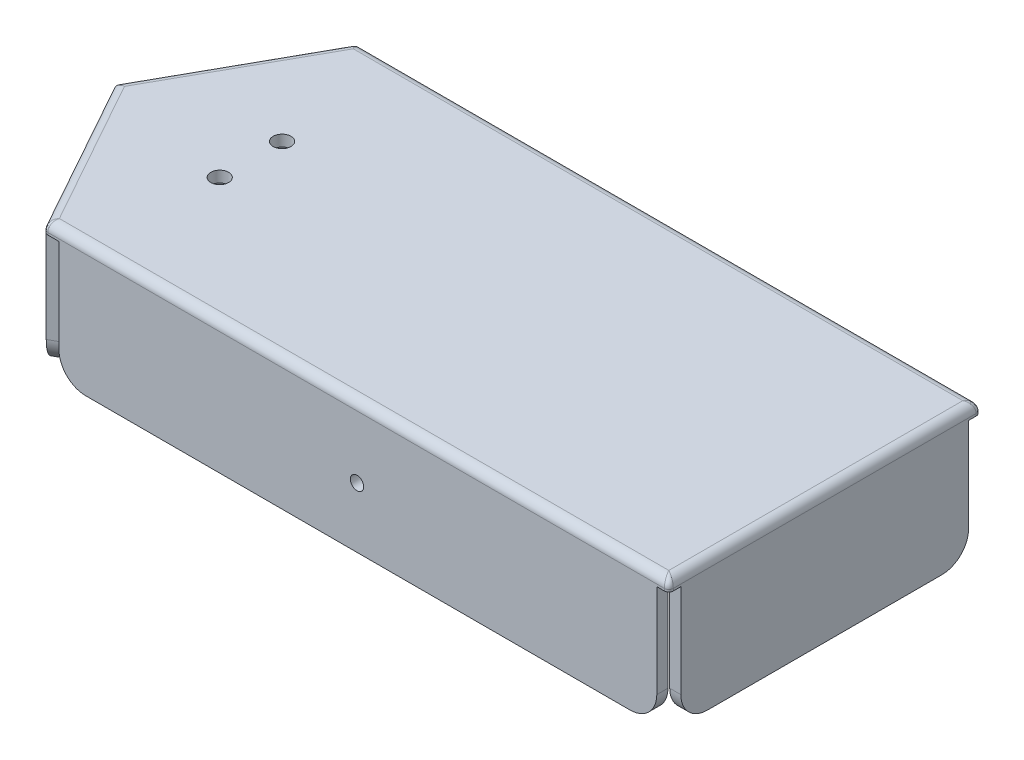
SolidWorks part; units mm, degrees
ref_plane "Alzado" through (0, 0, 0) normal (0, 0, 1) x (1, 0, 0)
ref_plane "Planta" through (0, 0, 0) normal (0, 1, 0) x (1, 0, 0)
ref_plane "Vista lateral" through (0, 0, 0) normal (1, 0, 0) x (0, 0, -1)
sketch "Croquis1" plane through (0, 0, 0) normal (0, 1, 0) x (1, 0, 0)
  line L1 (-69.4124, -35) -> (69, -35)
  line L3 (-69.4124, 35) -> (69, 35)
  line L4 (70, -34) -> (70, 34)
  line L5 (-70, -35) -> (70, 35) construction
  line L6 (-70, 35) -> (70, -35) construction
  line L8 (-70.286, 34.4867) -> (-89.5, 0)
  line L9 (-89.5, 0) -> (-70.286, -34.4867)
  arc A0 (69, 35) -> (70, 34) centre (69, 34) cw
  arc A1 (69, -35) -> (70, -34) centre (69, -34) ccw
  arc A2 (-69.4124, -35) -> (-70.286, -34.4867) centre (-69.4124, -34) cw
  arc A3 (-70.286, 34.4867) -> (-69.4124, 35) centre (-69.4124, 34) cw
  point P0 (0, 0)
  dimension "D3" = 1
  dimension "D1" = 140
  dimension "D2" = 70
  dimension "D4" = 40.0656
  dimension "D5" = 40.0656
extrude "Saliente-Extruir1" add sketch "Croquis1" along normal blind 2.5
sketch "Croquis4" plane through (0, 0, 0) normal (0, -1, 0) x (1, 0, 0)
  line L0 (-70.286, 34.4867) -> (-68.1021, 33.2699) construction
  line L1 (-68.1021, 33.2699) -> (-86.0993, 0.9672) construction
  line L2 (-86.0993, 0.9672) -> (-88.2832, 2.1839) construction
  line L3 (-89.5, 0) -> (-70.286, 34.4867) construction
  line L4 (-70.286, 34.4867) -> (-68.1021, 33.2699)
  line L5 (-68.1021, 33.2699) -> (-86.0993, 0.9672)
  line L6 (-86.0993, 0.9672) -> (-88.2832, 2.1839)
  line L7 (-88.2832, 2.1839) -> (-70.286, 34.4867)
  line L8 (-70.286, -34.4867) -> (-68.1461, -33.194)
  line L9 (-68.1461, -33.194) -> (-86.0993, -0.9672)
  line L10 (-86.0993, -0.9672) -> (-88.2832, -2.1839)
  line L11 (-70.286, -34.4867) -> (-89.5, 0) construction
  line L12 (-88.2832, -2.1839) -> (-70.286, -34.4867)
  line L13 (-66.9124, -35) -> (-66.9124, -32.5)
  line L14 (69, -35) -> (-69.4124, -35) construction
  line L15 (-66.9124, -32.5) -> (67.3, -32.5)
  line L16 (67.3, -32.5) -> (67.3, -35)
  line L17 (-66.9124, 35) -> (67.3, 35)
  line L18 (-69.4124, 35) -> (69, 35) construction
  line L19 (67.3, 35) -> (67.3, 32.5)
  line L20 (67.3, 32.5) -> (-66.9124, 32.5)
  line L21 (-66.9124, 32.5) -> (-66.9124, 35)
  line L22 (-66.9124, -35) -> (67.3, -35)
  line L23 (70, 32.3) -> (67.5, 32.3)
  line L24 (70, 34) -> (70, -34) construction
  line L25 (67.5, 32.3) -> (67.5, -32.3)
  line L26 (67.5, -32.3) -> (70, -32.3)
  line L27 (70, 32.3) -> (70, -32.3)
  dimension "D7" = 2.5
  dimension "D1" = 2.5
  dimension "D2" = 2.5
  dimension "D3" = 2.5
  dimension "D4" = 2.5
  dimension "D5" = 2.5
  dimension "D6" = 2.5
  dimension "D8" = 2.5
  dimension "D9" = 1.7
  dimension "D10" = 2.5
  dimension "D11" = 1.7
  dimension "D12" = 2.5
  dimension "D13" = 1.7
  dimension "D14" = 1.7
  dimension "D15" = 2.5
extrude "Saliente-Extruir3" add sketch "Croquis4" along normal blind 27
sketch "Croquis5" plane through (-68.2993, 0, 38.0525) normal (-0.8736, 0, 0.4867) x (0.4867, 0, 0.8736)
  line L0 (-41.0598, -27) -> (-41.0598, -21)
  line L1 (-41.0598, -27) -> (-41.0598, 0) construction
  line L2 (-41.0598, -21) -> (-27.0598, -27)
  line L3 (-4.0819, -27) -> (-41.0598, -27) construction
  line L4 (-27.0598, -27) -> (-41.0598, -27)
  line L7 (-10.0819, -27) -> (-4.0819, -27)
  line L9 (-4.0819, -27) -> (-4.0819, -21)
  arc A0 (-10.0819, -27) -> (-4.0819, -21) centre (-10.0819, -21) ccw
  point P16 (-4.0819, -27)
  point P17 (-4.0819, -27)
  dimension "D5" = 6
  dimension "D1" = 6
  dimension "D2" = 14
extrude "Cortar-Extruir3" cut sketch "Croquis5" against normal blind 27
sketch "Croquis6" plane through (-68.2993, 0, -38.0525) normal (-0.8736, 0, -0.4867) x (-0.4867, 0, 0.8736)
  line L0 (41.0598, -27) -> (41.0598, -21)
  line L1 (41.0598, -27) -> (41.0598, 0) construction
  line L2 (41.0598, -21) -> (27.0598, -27)
  line L3 (41.0598, -27) -> (4.0819, -27) construction
  line L4 (27.0598, -27) -> (41.0598, -27)
  line L5 (4.0819, -21) -> (4.0819, -27)
  line L6 (4.0819, -27) -> (10.0819, -27)
  arc A0 (10.0819, -27) -> (4.0819, -21) centre (10.0819, -21) cw
  point P16 (4.0819, -27)
  dimension "D5" = 6
  dimension "D1" = 6
  dimension "D2" = 14
extrude "Cortar-Extruir4" cut sketch "Croquis6" against normal blind 10
sketch "Croquis7" plane through (0, 0, 35) normal (0, 0, 1) x (1, 0, 0)
  line L0 (-66.9124, -21) -> (-66.9124, -27)
  line L2 (-66.9124, -27) -> (-60.9124, -27)
  line L4 (67.3, -21.0735) -> (67.3, -27)
  line L6 (67.3, -27) -> (58.9529, -27)
  arc A0 (-60.9124, -27) -> (-66.9124, -21) centre (-60.9124, -21) cw
  arc A1 (58.9529, -27) -> (67.3, -21.0735) centre (61.3141, -21.4841) ccw
  point P10 (-66.9124, -27)
  point P16 (67.3, -27)
  dimension "D3" = 6
  dimension "D4" = 6
sketch "Croquis8" plane through (70, 0, 0) normal (1, 0, 0) x (0, 0, -1)
  line L0 (-32.3, -21) -> (-32.3, -27)
  line L2 (-32.3, -27) -> (-26.3, -27)
  line L4 (32.3, -21) -> (32.3, -27)
  line L5 (32.3, -27) -> (26.3, -27)
  arc A0 (-26.3, -27) -> (-32.3, -21) centre (-26.3, -21) cw
  arc A1 (26.3, -27) -> (32.3, -21) centre (26.3, -21) ccw
  point P10 (-32.3, -27)
  point P19 (32.3, -27)
  dimension "D3" = 6
  dimension "D6" = 6
extrude "Cortar-Extruir6" cut sketch "Croquis8" against normal blind 10
sketch "Croquis10" plane through (0, 0, -35) normal (0, 0, -1) x (-1, 0, 0)
  line L0 (66.9124, -21) -> (66.9124, -27)
  line L2 (66.9124, -27) -> (60.9124, -27)
  line L4 (-58.9529, -27) -> (-67.3, -27)
  line L5 (-67.3, -27) -> (-67.3, -21.0735)
  arc A0 (60.9124, -27) -> (66.9124, -21) centre (60.9124, -21) ccw
  arc A1 (-58.9529, -27) -> (-67.3, -21.0735) centre (-61.3141, -21.4841) cw
  point P17 (66.9124, -27)
  point P20 (-67.3, -27)
  dimension "D5" = 6
sketch "Croquis11" plane through (0, 0, 35) normal (0, 0, 1) x (1, 0, 0)
  line L0 (61.3, -27) -> (67.3, -27)
  line L2 (67.3, -27) -> (67.3, -21)
  line L4 (-60.9124, -27) -> (-66.9124, -27)
  line L5 (-66.9124, -27) -> (-66.9124, -21)
  arc A0 (61.3, -27) -> (67.3, -21) centre (61.3, -21) ccw
  arc A1 (-60.9124, -27) -> (-66.9124, -21) centre (-60.9124, -21) cw
  point P16 (67.3, -27)
  point P19 (-66.9124, -27)
  dimension "D5" = 6
extrude "Cortar-Extruir8" cut sketch "Croquis11" against normal blind 10
sketch "Croquis12" plane through (0, 0, -35) normal (0, 0, -1) x (-1, 0, 0)
  line L0 (-67.3, -21) -> (-67.3, -27)
  line L3 (-67.3, -27) -> (-61.3, -27)
  line L5 (66.9124, -21) -> (66.9124, -27)
  line L6 (66.9124, -27) -> (60.9124, -27)
  arc A0 (-61.3, -27) -> (-67.3, -21) centre (-61.3, -21) cw
  arc A1 (60.9124, -27) -> (66.9124, -21) centre (60.9124, -21) ccw
  point P17 (-67.3, -27)
  point P20 (66.9124, -27)
  dimension "D5" = 6
extrude "Cortar-Extruir9" cut sketch "Croquis12" against normal blind 10
fillet "Redondeo2" radius 2 9 edges at (-69.919, 2.5, -34.8622) (69.7071, 2.5, -34.7071) (69.7071, 2.5, 34.7071) (-69.919, 2.5, 34.8622) (-0.2062, 2.5, 35) (70, 2.5, 0) (-0.2062, 2.5, -35) (-79.893, 2.5, -17.2434) (-79.893, 2.5, 17.2434)
sketch "Croquis13" plane through (0, 2.5, 0) normal (0, 1, 0) x (1, 0, 0)
  line L0 (-68.8248, 33) -> (-58.8248, 33) construction
  line L1 (68, 33) -> (-68.8248, 33) construction
  line L2 (-58.8248, 33) -> (-58.8248, -33) construction
  line L3 (-68.8248, -33) -> (68, -33) construction
  line L4 (-58.8248, 0) -> (-58.8248, 7) construction
  line L5 (-58.8248, 0) -> (-58.8248, -7) construction
  circle A0 centre (-58.8248, 7) radius 2
  circle A1 centre (-58.8248, -7) radius 2
  dimension "D3" = 7
  dimension "D1" = 10
  dimension "D2" = 7
extrude "Cortar-Extruir10" cut sketch "Croquis13" against normal blind 10
sketch "Croquis14" plane through (0, 0, 35) normal (0, 0, 1) x (1, 0, 0)
  line L0 (0, 0) -> (0, -13.5) construction
  line L1 (0, -13.5) -> (45, -13.5) construction
  line L2 (0, -13.5) -> (-45, -13.5) construction
  circle A2 centre (0, -13.5) radius 1.5
  dimension "D2" = 3
  dimension "D1" = 13.5
extrude "Cortar-Extruir11" cut sketch "Croquis14" against normal blind 200
